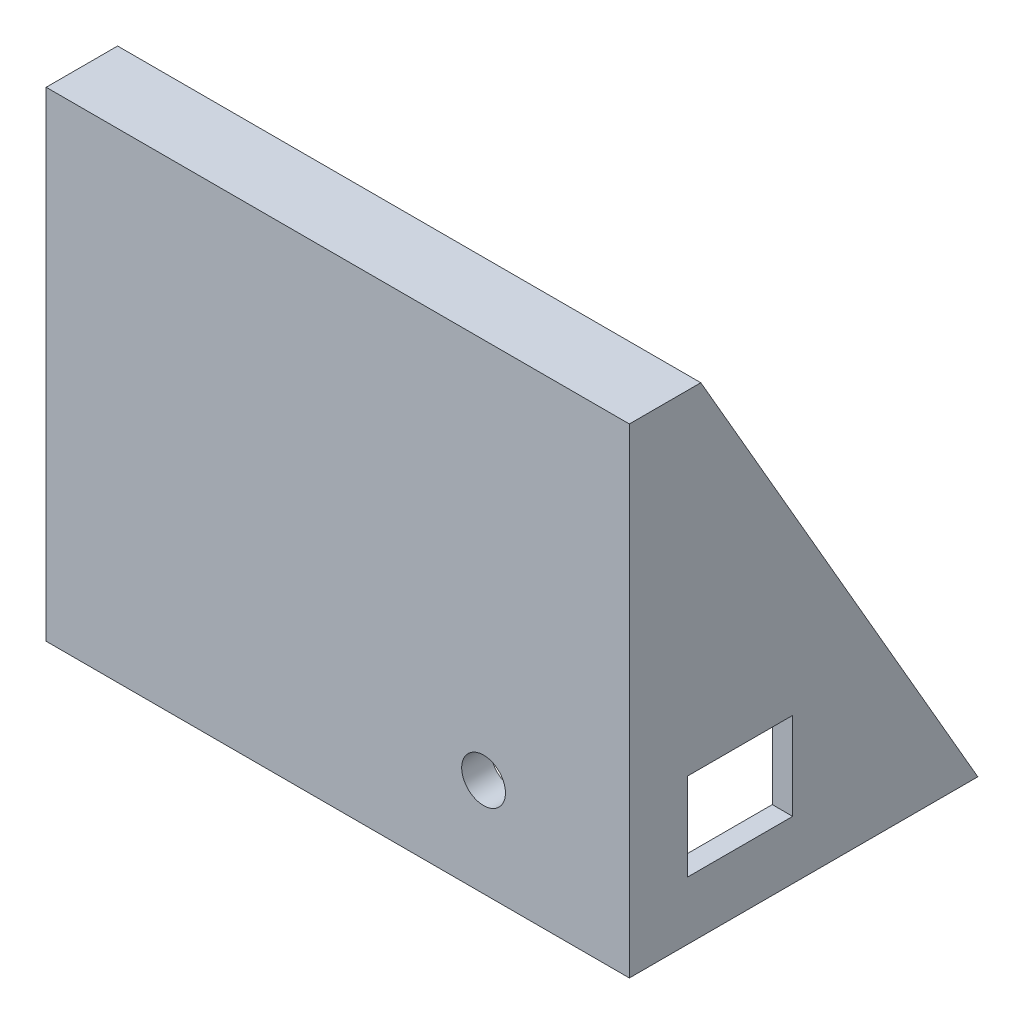
SolidWorks part; units mm, degrees
material "ABS"
ref_plane "Front Plane" through (0, 0, 0) normal (0, 0, 1) x (1, 0, 0)
ref_plane "Top Plane" through (0, 0, 0) normal (0, 1, 0) x (1, 0, 0)
ref_plane "Right Plane" through (0, 0, 0) normal (1, 0, 0) x (0, 0, -1)
sketch "Sketch2" plane through (0, 0, 0) normal (1, 0, 0) x (0, 0, -1)
  line L0 (0, 60.7895) -> (24.5, 60.7895)
  line L1 (24.5, 60.7895) -> (119.5, -103.7554)
  line L2 (119.5, -103.7554) -> (0, -103.7554)
  line L3 (0, -103.7554) -> (0, 60.7895)
  dimension "D1" = 24.5
  dimension "D2" = 190
  dimension "D3" = 120
extrude "Boss-Extrude1" add sketch "Sketch2" along normal blind 200
shell "Shell1" thickness 10 removed face at (100, -103.7554, -59.75)
sketch "Sketch4" plane through (0, 25.8062, -44.6976) normal (0, 0.5, -0.866) x (-1, 0, 0)
  line L0 (-200, 40.3952) -> (0, 40.3952) construction
  line L1 (-200, -149.6048) -> (-200, 40.3952) construction
  line L3 (0, -149.6048) -> (0, 40.3952) construction
  line L4 (-200, -149.6048) -> (0, -149.6048) construction
  circle A0 centre (-185, 0.3952) radius 2.5
  circle A1 centre (-185, -109.6048) radius 2.5
  circle A2 centre (-155, -139.6048) radius 2.5
  circle A3 centre (-45, -139.6048) radius 2.5
  circle A4 centre (-15, -109.6048) radius 2.5
  circle A5 centre (-15, 0.3952) radius 2.5
  circle A6 centre (-45, 30.3952) radius 2.5
  circle A7 centre (-155, 30.3952) radius 2.5
  dimension "D1" = 5
  dimension "D2" = 5
  dimension "D3" = 5
  dimension "D4" = 5
  dimension "D5" = 5
  dimension "D6" = 5
  dimension "D7" = 5
  dimension "D8" = 5
  dimension "D10" = 15
  dimension "D11" = 40
  dimension "D12" = 45
  dimension "D13" = 45
  dimension "D14" = 15
  dimension "D15" = 10
  dimension "D16" = 40
  dimension "D17" = 40
  dimension "D18" = 15
  dimension "D19" = 10
  dimension "D20" = 45
  dimension "D21" = 15
  dimension "D22" = 40
  dimension "D23" = 10
  dimension "D24" = 45
  dimension "D9" = 10
extrude "Cut-Extrude2" cut sketch "Sketch4" against normal blind 5
sketch "Sketch5" plane through (200, 0, 0) normal (1, 0, 0) x (0, 0, -1)
  line L0 (0, 60.7895) -> (0, -103.7554) construction
  line L1 (20, -53.7554) -> (56, -53.7554)
  line L2 (20, -53.7554) -> (20, -83.7554)
  line L3 (20, -83.7554) -> (56, -83.7554)
  line L4 (56, -53.7554) -> (56, -83.7554)
  line L5 (0, -103.7554) -> (119.5, -103.7554) construction
  point P6 (20, -68.7554)
  dimension "D1" = 36
  dimension "D2" = 30
  dimension "D3" = 20
  dimension "D4" = 20
extrude "Cut-Extrude3" cut sketch "Sketch5" against normal blind 20
sketch "Sketch6" plane through (0, 0, 0) normal (0, 0, 1) x (1, 0, 0)
  line L0 (200, 60.7895) -> (200, -103.7554) construction
  line L1 (193, -103.7554) -> (7, -103.7554) construction
  circle A0 centre (150, -70.0359) radius 7.5
  dimension "D1" = 15
  dimension "D2" = 50
extrude "Cut-Extrude4" cut sketch "Sketch6" against normal blind 20
sketch "Sketch7" plane through (0, 0, 0) normal (0, 0, 1) x (1, 0, 0)
  line L0 (200, -103.7554) -> (0, -103.7554) construction
  line L1 (0, 60.7895) -> (200, 60.7895)
  line L2 (0, 60.7895) -> (0, -103.7554)
  line L3 (0, -103.7554) -> (200, -103.7554)
  line L4 (200, 60.7895) -> (200, -103.7554)
extrude "Boss-Extrude2" [suppressed] add sketch "Sketch7" along normal blind 60
sketch "Sketch8" plane through (0, 0, -10) normal (0, 0, -1) x (-1, 0, 0)
  circle A0 centre (-150, -70.0359) radius 7.5
extrude "Cut-Extrude5" [suppressed] cut sketch "Sketch8" against normal through all
sketch "Sketch14" plane through (0, 60.7895, 0) normal (0, 1, 0) x (1, 0, 0)
  line L0 (0, -60) -> (-6.1272, -62.0017)
  line L1 (-6.1272, -62.0017) -> (0, -51.8189)
  line L2 (200, -60) -> (206.2634, -60)
  line L3 (206.2634, -60) -> (203.6169, -51.899)
  line L4 (203.6169, -51.899) -> (200, -51.899)
  line L8 (0, -51.8189) -> (0, -60)
  line L9 (0, -60) -> (200, -60)
  line L10 (200, -60) -> (200, -51.899)
  spline S2 degree 3 poles (200, -51.899) (198.8085, -50.8812) (197.5963, -49.8841) (194.763, -47.639) (193.1253, -46.4034) (188.1518, -42.829) (184.7446, -40.6125) (177.7611, -36.4874) (174.1845, -34.5791) (166.8707, -31.0548) (163.134, -29.4377) (157.4116, -27.2257) (155.4927, -26.5272) (151.6403, -25.2084) (149.7056, -24.5876) (143.8764, -22.8379) (139.957, -21.8218) (132.0538, -20.0801) (128.07, -19.3547) (122.0464, -18.483) (120.0305, -18.2286) (115.9827, -17.7924) (113.9494, -17.6105) (107.8336, -17.1755) (103.7701, -17.0354) (91.619, -17.0522) (83.571, -17.6433) (71.578, -19.3991) (67.5936, -20.1303) (61.6376, -21.4536) (59.6557, -21.9326) (55.699, -22.9683) (53.737, -23.5218) (47.9015, -25.2879) (44.0776, -26.6062) (36.5638, -29.5265) (32.8738, -31.1287) (25.6323, -34.6265) (22.0813, -36.5233) (15.1288, -40.6338) (11.7272, -42.8472) (7.5776, -45.8312) (6.7517, -46.4398) (5.1169, -47.6744) (4.3082, -48.3002) (2.3195, -49.8771) (1.15, -50.8385) (0, -51.8189) knots 0.222344 0.222344 0.222344 0.222344 0.234375 0.234375 0.25 0.25 0.28125 0.28125 0.3125 0.3125 0.34375 0.34375 0.359375 0.359375 0.375 0.375 0.40625 0.40625 0.4375 0.4375 0.453125 0.453125 0.46875 0.46875 0.5 0.5 0.5625 0.5625 0.59375 0.59375 0.609375 0.609375 0.625 0.625 0.65625 0.65625 0.6875 0.6875 0.71875 0.71875 0.75 0.75 0.757812 0.757812 0.765625 0.765625 0.777234 0.777234 0.777234 0.777234
  line M17 (0, 24.5) -> (0, 0)
  line M19 (200, 0) -> (200, 24.5)
extrude "Cut-Extrude7" [suppressed] cut sketch "Sketch14" against normal through all contours L3 L4 L2 M19 | L10 S2 L9 M17 | L8 L1 L0
sketch "Sketch16" [suppressed] plane through (0, 60.7895, 0) normal (0, 1, 0) x (1, 0, 0)
  line L0 (200, -51.899) -> (217.6123, -51.899)
  line L1 (217.6123, -51.899) -> (217.6123, -73.519)
  line L2 (217.6123, -73.519) -> (206.6918, -73.519)
  line L3 (-9.5151, -73.519) -> (-9.5151, -51.899)
  line L4 (-9.5151, -51.899) -> (200, -51.899)
  line L5 (206.6918, -73.519) -> (-9.5151, -73.519)
extrude "Cut-Extrude8" [suppressed] cut sketch "Sketch16" against normal through all
